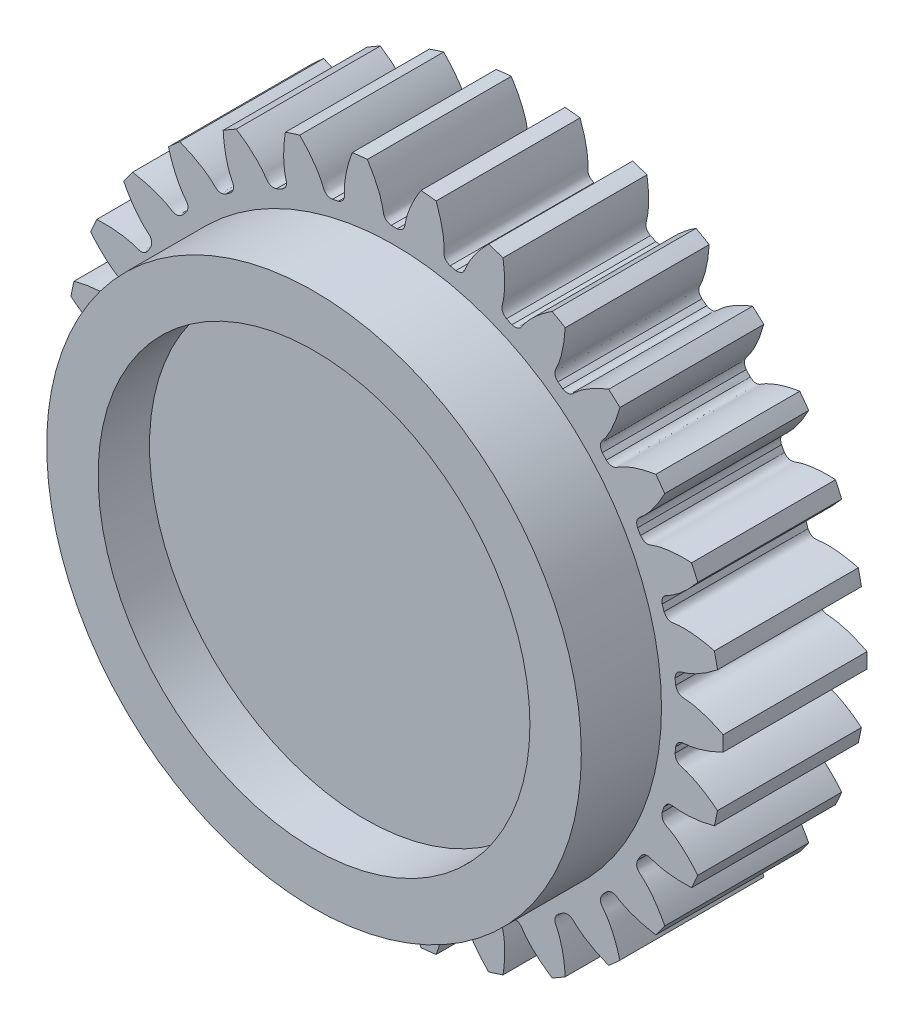
SolidWorks part; units mm, degrees
ref_plane "前视基准面" through (0, 0, 0) normal (0, 0, 1) x (1, 0, 0)
ref_plane "上视基准面" through (0, 0, 0) normal (0, 1, 0) x (1, 0, 0)
ref_plane "右视基准面" through (0, 0, 0) normal (1, 0, 0) x (0, 0, -1)
sketch "草图1" plane through (0, 0, 0) normal (0, 0, 1) x (1, 0, 0)
  circle A0 centre (0, 0) radius 16
extrude "凸台-拉伸1" add sketch "草图1" along normal blind 7
ref_axis "基准轴1" [suppressed] through (0, 0, -0.35) along (0, 0, 1)
sketch "草图2" plane through (0, 0, 0) normal (0, 0, 1) x (1, 0, 0)
  line L0 (0, 0) -> (0, 16) construction
  circle A0 centre (0, 0) radius 16 construction
  arc A1 (0.1456, 13.7492) -> (-0.1456, 13.7492) centre (0, 0) ccw
  arc A2 (3.3663, 18.1906) -> (-3.3663, 18.1906) centre (0, 0) ccw
  spline S0 degree 3 poles (0.1456, 13.7492) (0.5082, 13.813) (0.5103, 14.0471) (0.559, 14.2886) (0.57, 14.3381) (0.5832, 14.3929) (0.5991, 14.4529) (0.6176, 14.518) (0.6391, 14.588) (0.6638, 14.663) (0.6918, 14.7428) (0.7234, 14.8273) (0.7588, 14.9164) (0.7981, 15.01) (0.8416, 15.1079) (0.8894, 15.21) (0.9417, 15.3163) (0.9987, 15.4264) (1.0606, 15.5404) (1.1276, 15.658) (1.1998, 15.779) (1.2774, 15.9034) (1.3605, 16.031) (1.4494, 16.1615) (1.5441, 16.2948) (1.6448, 16.4307) (1.7516, 16.569) (1.8647, 16.7096) (1.9843, 16.8522) (2.1103, 16.9966) (2.2431, 17.1427) (2.3825, 17.2901) (2.5289, 17.4388) (2.6823, 17.5884) (2.8427, 17.7389) (3.0689, 17.9426) (3.2453, 18.0921) (3.3663, 18.1906) knots 0 0 0 0 0.115324 0.123413 0.132512 0.142623 0.153745 0.165878 0.179022 0.193177 0.208343 0.22452 0.241708 0.259907 0.279117 0.299338 0.320571 0.342814 0.366068 0.390334 0.41561 0.441898 0.469196 0.497506 0.526827 0.557158 0.588501 0.620855 0.65422 0.688595 0.723982 0.76038 0.797789 0.836209 0.87564 0.916083 1 1 1 1
  spline S1 degree 3 poles (-0.1456, 13.7492) (-0.5082, 13.813) (-0.5103, 14.0471) (-0.559, 14.2886) (-0.57, 14.3381) (-0.5832, 14.3929) (-0.5991, 14.4529) (-0.6176, 14.518) (-0.6391, 14.588) (-0.6638, 14.663) (-0.6918, 14.7428) (-0.7234, 14.8273) (-0.7588, 14.9164) (-0.7981, 15.01) (-0.8416, 15.1079) (-0.8894, 15.21) (-0.9417, 15.3163) (-0.9987, 15.4264) (-1.0606, 15.5404) (-1.1276, 15.658) (-1.1998, 15.779) (-1.2774, 15.9034) (-1.3605, 16.031) (-1.4494, 16.1615) (-1.5441, 16.2948) (-1.6448, 16.4307) (-1.7516, 16.569) (-1.8647, 16.7096) (-1.9843, 16.8522) (-2.1103, 16.9966) (-2.2431, 17.1427) (-2.3825, 17.2901) (-2.5289, 17.4388) (-2.6823, 17.5884) (-2.8427, 17.7389) (-3.0689, 17.9426) (-3.2453, 18.0921) (-3.3663, 18.1906) knots 0 0 0 0 0.115324 0.123413 0.132512 0.142623 0.153745 0.165878 0.179022 0.193177 0.208343 0.22452 0.241708 0.259907 0.279117 0.299338 0.320571 0.342814 0.366068 0.390334 0.41561 0.441898 0.469196 0.497506 0.526827 0.557158 0.588501 0.620855 0.65422 0.688595 0.723982 0.76038 0.797789 0.836209 0.87564 0.916083 1 1 1 1
extrude "切除-拉伸1" cut sketch "草图2" along normal through all
pattern_circular "阵列(圆周)1" count 30 every 12 about axis through (0, 0, -0.35) along (0, 0, 1) of "切除-拉伸1"
sketch "草图3" plane through (0, 0, 0) normal (0, 0, 1) x (1, 0, 0)
  circle A0 centre (0, 0) radius 15 construction
  dimension "Dn" = 30
sketch "草图5" plane through (0, 0, 7) normal (0, 0, 1) x (1, 0, 0)
  circle A0 centre (0, 0) radius 13
  dimension "D1" = 26
extrude "凸台-拉伸3" add sketch "草图5" along normal blind 1.4
sketch "草图4" plane through (0, 0, 8.4) normal (0, 0, 1) x (1, 0, 0)
  circle A0 centre (0, 0) radius 10.5
  circle A1 centre (0, 0) radius 13
  dimension "D1" = 21
  dimension "D2" = 26
extrude "凸台-拉伸2" add sketch "草图4" along normal blind 2.5
